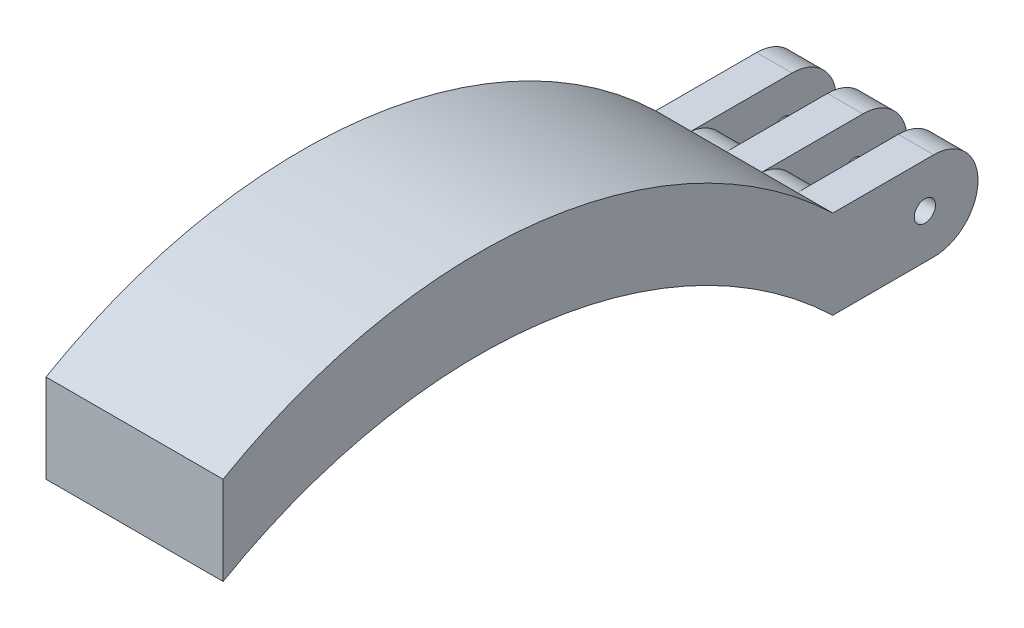
SolidWorks part; units mm, degrees
ref_plane "Front Plane" through (0, 0, 0) normal (0, 0, 1) x (1, 0, 0)
ref_plane "Top Plane" through (0, 0, 0) normal (0, 1, 0) x (1, 0, 0)
ref_plane "Right Plane" through (0, 0, 0) normal (1, 0, 0) x (0, 0, -1)
sketch "Sketch2" plane through (0, 0, 0) normal (0, 0, 1) x (1, 0, 0)
  line L0 (0, 0) -> (50, 0)
  line L1 (50, 0) -> (50, 25)
  line L2 (50, 25) -> (0, 25)
  line L3 (0, 25) -> (0, 0)
extrude "Boss-Extrude1" add sketch "Sketch2" along normal blind 40 and the other way blind 1
sketch "Sketch5" plane through (0, 0, -1) normal (0, 0, -1) x (-1, 0, 0)
  line L2 (-40, 25) -> (-30, 25)
  line L8 (-50, 25) -> (0, 25) construction
  line L13 (-10, 0) -> (-10, 25)
  line L16 (-20, 25) -> (-10, 25)
  line L17 (-40, 25) -> (-40, 0)
  line L18 (0, 0) -> (-50, 0) construction
  line L19 (-40, 0) -> (-30, 0)
  line L20 (-30, 0) -> (-30, 25)
  line L21 (-20, 25) -> (-20, 0)
  line L22 (-20, 0) -> (-10, 0)
extrude "Cut-Extrude2" cut sketch "Sketch5" against normal blind 30
sketch "Sketch7" plane through (50, 0, 0) normal (1, 0, 0) x (0, 0, -1)
  line L5 (-212.111, 20.9769) -> (-212.111, 45.9769)
  line L6 (-40, 25) -> (-40, 0)
  arc A2 (-212.111, 20.9769) -> (-40, 0) centre (-140, -103.923) cw
  arc A3 (-212.111, 45.9769) -> (-40, 25) centre (-140, -78.923) cw
extrude "Boss-Extrude2" add sketch "Sketch7" against normal blind 50
sketch "Sketch8" plane through (0, 0, 0) normal (0, -1, 0) x (-1, 0, 0)
  circle A0 centre (-36.75, -185) radius 3
  circle A1 centre (-12.25, -185) radius 3
extrude "Cut-Extrude4" cut sketch "Sketch8" against normal blind 49
sketch "Sketch9" plane through (0, 0, 0) normal (0, -1, 0) x (-1, 0, 0)
  circle A0 centre (-24.5, -65) radius 5
extrude "Cut-Extrude5" cut sketch "Sketch9" against normal blind 26
sketch "Sketch10" plane through (50, 0, 0) normal (1, 0, 0) x (0, 0, -1)
  circle A0 centre (-14, 12.5) radius 3
extrude "Cut-Extrude6" cut sketch "Sketch10" against normal blind 52
fillet "Fillet1" radius 12.5 6 edges at (45, 0, -1) (25, 0, -1) (5, 0, -1) (5, 25, -1) (25, 25, -1) (45, 25, -1)
fillet "Fillet2" radius 12.5 4 edges at (15, 0, 29) (15, 25, 29) (35, 0, 29) (35, 25, 29)
